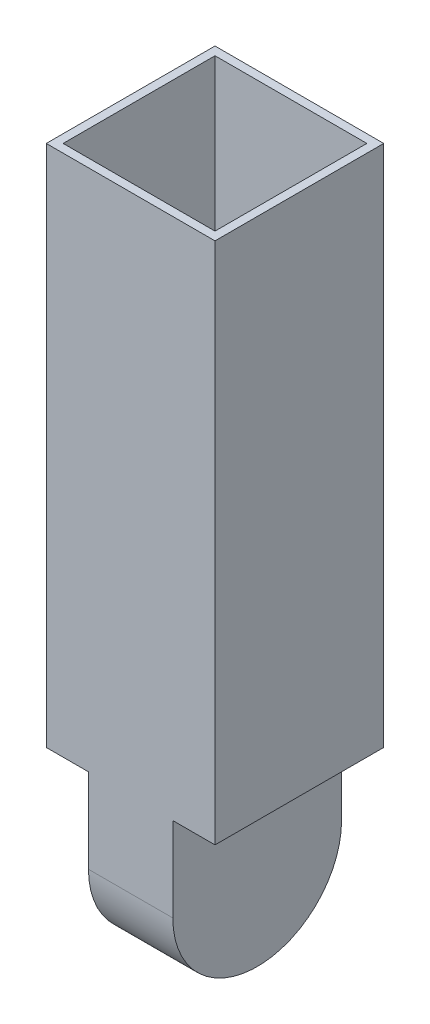
SolidWorks part; units mm, degrees
ref_plane "Front" through (0, 0, 0) normal (0, 0, 1) x (1, 0, 0)
ref_plane "Top" through (0, 0, 0) normal (0, 1, 0) x (1, 0, 0)
ref_plane "Right" through (0, 0, 0) normal (1, 0, 0) x (0, 0, -1)
sketch "草图1" plane through (0, 0, 0) normal (0, 1, 0) x (1, 0, 0)
  line L1 (-10, 10) -> (10, 10)
  line L2 (-10, 10) -> (-10, -10)
  line L3 (-10, -10) -> (10, -10)
  line L4 (10, 10) -> (10, -10)
  line L5 (-9, 9) -> (9, 9)
  line L6 (-9, 9) -> (-9, -9)
  line L7 (-9, -9) -> (9, -9)
  line L8 (9, 9) -> (9, -9)
  dimension "D1" = 20
  dimension "D2" = 20
  dimension "D3" = 10
  dimension "D4" = 10
  dimension "D5" = 18
  dimension "D6" = 18
  dimension "D7" = 9
  dimension "D8" = 9
extrude "凸台-拉伸1" add sketch "草图1" along normal blind 60
sketch "草图2" plane through (0, 0, 0) normal (0, -1, 0) x (1, 0, 0)
  line L1 (-10, 10) -> (10, 10)
  line L2 (-10, 10) -> (-10, -10)
  line L3 (-10, -10) -> (10, -10)
  line L4 (10, 10) -> (10, -10)
extrude "凸台-拉伸2" add sketch "草图2" along normal blind 2
sketch "草图6" plane through (0, 0, 0) normal (1, 0, 0) x (0, 0, -1)
  line L0 (10, -2) -> (-10, -2) construction
  line L1 (-10, -2) -> (10, -2)
  line L3 (-10, -12) -> (-10, -2)
  line L5 (10, -12) -> (10, -2)
  arc A0 (-10, -12) -> (10, -12) centre (0, -12) ccw
  dimension "D1" = 10
extrude "凸台-拉伸3" add sketch "草图6" along normal mid plane 10
